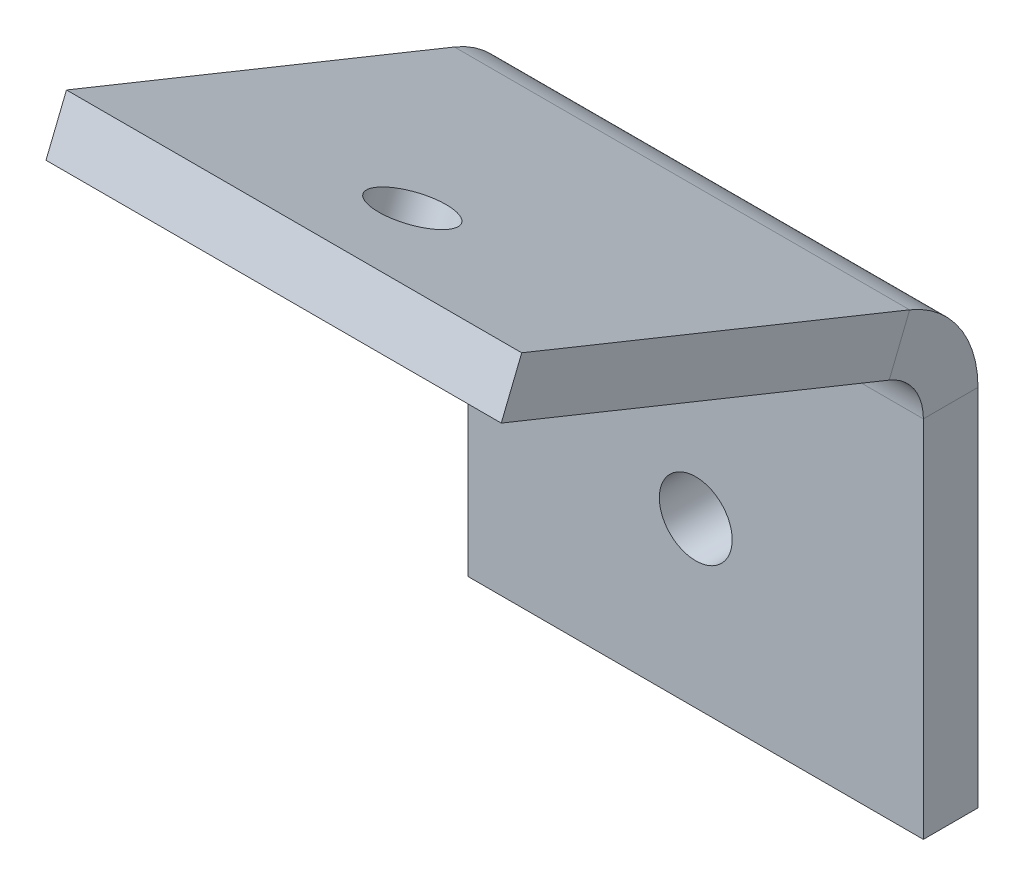
SolidWorks part; units mm, degrees
note: The reader was unsure of these and kept them because the rebuilt part matched: flange length of "Edge-Flange1".
ref_plane "Front Plane" through (0, 0, 0) normal (0, 0, 1) x (1, 0, 0)
ref_plane "Top Plane" through (0, 0, 0) normal (0, 1, 0) x (1, 0, 0)
ref_plane "Right Plane" through (0, 0, 0) normal (1, 0, 0) x (0, 0, -1)
sketch "Sketch1" plane through (0, 0, 0) normal (0, 0, 1) x (1, 0, 0)
  line L1 (-4.5283, -4.2453) -> (20.4717, -4.2453)
  line L2 (-4.5283, -4.2453) -> (-4.5283, 15.7547)
  line L3 (-4.5283, 15.7547) -> (20.4717, 15.7547)
  line L4 (20.4717, -4.2453) -> (20.4717, 15.7547)
  circle A0 centre (7.9717, 4.7547) radius 2
  dimension "D3" = 4
  dimension "D4" = 9
  dimension "D5" = 12.5
  dimension "D1" = 20
  dimension "D2" = 25
base flange "Base-Flange1" sketch "Sketch1" thickness 3 reverse thickness direction no parameters "D1"=3
edge flange "Edge-Flange1" sketch "Sketch8" flange angle 112 flange length 27.0235 flange position bend outside bend radius 3 thickness 3 relief rectangular parameters "D6"=10
sketch "Sketch8" plane through (0, 15.7547, 0) normal (0, 0.9272, -0.3746) x (-1, 0, 0)
  line L0 (-20.4717, 0) -> (4.5283, 0) construction
  line L1 (-20.4717, 0) -> (4.5283, 0)
  line L2 (-20.4717, 0) -> (-20.4717, 25)
  line L3 (-20.4717, 25) -> (4.5283, 25)
  line L4 (4.5283, 25) -> (4.5283, 0)
  circle A0 centre (-7.9717, 18) radius 2
  dimension "D2" = 4
  dimension "D3" = 5
  dimension "D4" = 12.5
  dimension "D1" = 25
bend "EdgeBend1" bend radius 3 bend angle 68 parameters "D5"=1
sketch "Bend-Lines1" [suppressed] plane through (0, 0, 0) normal (0, 1, 0) x (1, 0, 0)
sketch "Bounding-Box1" [suppressed] plane through (0, 0, 0) normal (0, 1, 0) x (1, 0, 0)
sheet metal parameters "Sheet-Metal1" thickness 3 parameters "D1"=0.7366
flat pattern "Flat-Pattern1" [suppressed]
sketch "Bend-Lines2" plane through (0, 0, 0) normal (0, 1, 0) x (1, 0, 0)
sketch3d "Bounding-Box2" [suppressed]
  line L0 (4.5283, -4.2453, 0) -> (-15.4717, -4.2453, 0) construction
  line L1 (4.5283, 10.7547, 0) -> (-15.4717, 10.7547, 0) construction
  line L2 (4.5283, -4.2453, 0) -> (4.5283, 10.7547, 0) construction
  line L3 (-15.4717, -4.2453, 0) -> (-15.4717, 10.7547, 0) construction
sheet metal parameters "Sheet-Metal2" thickness 3 parameters "D1"=0.7366
flat pattern "Flat-Pattern1"
sketch "Bend-Lines2" plane through (0, 0, 0) normal (0, 0, 1) x (1, 0, 0)
  line L0 (20.4717, 17.1418) -> (-4.5283, 17.1418) construction
  line L1 (20.4717, 17.1418) -> (-4.5283, 17.1418) construction
sketch3d "Bounding-Box2" [suppressed]
  line L0 (20.4717, 41.5053, 0) -> (20.4717, -4.2453, 0) construction
  line L1 (-4.5283, 41.5053, 0) -> (-4.5283, -4.2453, 0) construction
  line L2 (20.4717, 41.5053, 0) -> (-4.5283, 41.5053, 0) construction
  line L3 (20.4717, -4.2453, 0) -> (-4.5283, -4.2453, 0) construction
bend of the flat pattern "Flatten-<EdgeBend1>1"
